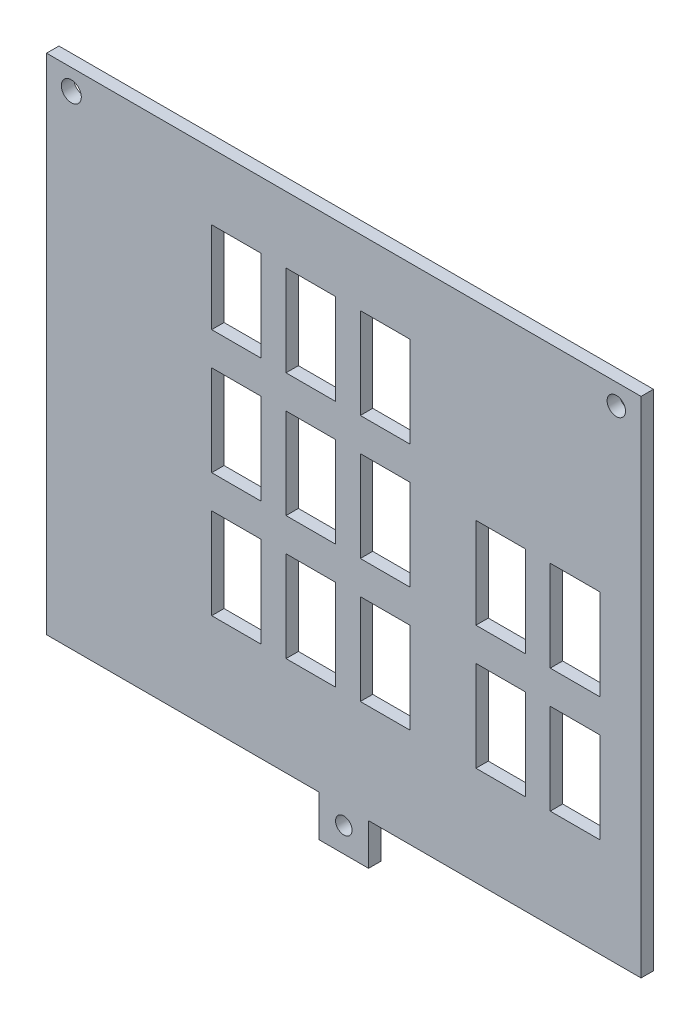
SolidWorks part; units mm, degrees
ref_plane "Plan de face" through (0, 0, 0) normal (0, 0, 1) x (1, 0, 0)
ref_plane "Plan de dessus" through (0, 0, 0) normal (0, 1, 0) x (1, 0, 0)
ref_plane "Plan de droite" through (0, 0, 0) normal (1, 0, 0) x (0, 0, -1)
sketch "Esquisse1" plane through (0, 0, 0) normal (0, 0, 1) x (1, 0, 0)
  line L0 (-67.585, 27.7309) -> (4.415, 27.7309)
  line L1 (4.415, 27.7309) -> (4.415, -33.2691)
  line L2 (4.415, -33.2691) -> (-67.585, -33.2691)
  line L3 (-67.585, -33.2691) -> (-67.585, 27.7309)
extrude "Boss.-Extru.1" add sketch "Esquisse1" along normal blind 1.5
sketch "Esquisse2" plane through (0, 0, 0) normal (0, 0, -1) x (-1, 0, 0)
  line L0 (-4.415, 27.7309) -> (67.585, 27.7309) construction
  line L1 (67.585, 27.7309) -> (67.585, -33.2691) construction
  line L2 (-4.415, -33.2691) -> (-4.415, 27.7309) construction
  circle A0 centre (-1.415, 25.2309) radius 1.1145
  circle A1 centre (64.585, 25.2309) radius 1.2071
  dimension "D1" = 2.5
  dimension "D2" = 2.5
  dimension "D3" = 3
  dimension "D4" = 3
extrude "Enlèv. mat.-Extru.1" cut sketch "Esquisse2" against normal through all
sketch "Esquisse4" plane through (0, 0, 0) normal (0, 0, -1) x (-1, 0, 0)
  line L0 (29.585, -21.2691) -> (29.585, -10.2691)
  line L1 (67.585, -33.2691) -> (-4.415, -33.2691) construction
  line L2 (29.585, -10.2691) -> (23.585, -10.2691)
  line L3 (29.585, 8.7309) -> (29.585, 19.7309)
  line L4 (67.585, 27.7309) -> (67.585, -33.2691) construction
  line L5 (23.585, -10.2691) -> (23.585, -21.2691)
  line L6 (47.585, -21.2691) -> (41.585, -21.2691)
  line L7 (41.585, -21.2691) -> (41.585, -10.2691)
  line L8 (41.585, -10.2691) -> (47.585, -10.2691)
  line L9 (47.585, -10.2691) -> (47.585, -21.2691)
  line L10 (23.585, -21.2691) -> (29.585, -21.2691)
  line L11 (38.585, -21.2691) -> (38.585, -10.2691)
  line L12 (38.585, -10.2691) -> (32.585, -10.2691)
  line L13 (32.585, -10.2691) -> (32.585, -21.2691)
  line L14 (32.585, -21.2691) -> (38.585, -21.2691)
  line L15 (47.585, -6.2691) -> (47.585, 4.7309)
  line L16 (47.585, 4.7309) -> (41.585, 4.7309)
  line L17 (41.585, 4.7309) -> (41.585, -6.2691)
  line L18 (41.585, -6.2691) -> (47.585, -6.2691)
  line L19 (38.585, -6.2691) -> (38.585, 4.7034)
  line L20 (38.585, 4.7034) -> (32.585, 4.7034)
  line L21 (32.585, 4.7034) -> (32.585, -6.2691)
  line L22 (32.585, -6.2691) -> (38.585, -6.2691)
  line L23 (29.585, -6.2691) -> (29.585, 4.7309)
  line L24 (29.585, 4.7309) -> (23.585, 4.7309)
  line L25 (23.585, 4.7309) -> (23.585, -6.2691)
  line L26 (23.585, -6.2691) -> (29.585, -6.2691)
  line L27 (29.585, 19.7309) -> (23.585, 19.7309)
  line L28 (23.585, 19.7309) -> (23.585, 8.7309)
  line L29 (23.585, 8.7309) -> (29.585, 8.7309)
  line L30 (38.585, 8.7034) -> (38.585, 19.7034)
  line L31 (38.585, 19.7034) -> (32.585, 19.7034)
  line L32 (32.585, 19.7034) -> (32.585, 8.7034)
  line L33 (32.585, 8.7034) -> (38.585, 8.7034)
  line L34 (47.585, 8.7309) -> (47.585, 19.7309)
  line L35 (47.585, 19.7309) -> (41.585, 19.7309)
  line L36 (41.585, 19.7309) -> (41.585, 8.7309)
  line L37 (41.585, 8.7309) -> (47.585, 8.7309)
  line L38 (15.585, -21.2691) -> (9.585, -21.2691)
  line L39 (9.585, -21.2691) -> (9.585, -10.2691)
  line L40 (9.585, -10.2691) -> (15.585, -10.2691)
  line L41 (15.585, -10.2691) -> (15.585, -21.2691)
  line L42 (6.585, -21.2691) -> (0.585, -21.2691)
  line L43 (0.585, -21.2691) -> (0.585, -10.2691)
  line L44 (0.585, -10.2691) -> (6.585, -10.2691)
  line L45 (6.585, -10.2691) -> (6.585, -21.2691)
  line L46 (15.585, -6.2691) -> (9.585, -6.2691)
  line L47 (9.585, -6.2691) -> (9.585, 4.7309)
  line L48 (9.585, 4.7309) -> (15.585, 4.7309)
  line L49 (15.585, 4.7309) -> (15.585, -6.2691)
  line L50 (6.585, -6.2691) -> (0.585, -6.2691)
  line L51 (0.585, -6.2691) -> (0.585, 4.7309)
  line L52 (0.585, 4.7309) -> (6.585, 4.7309)
  line L53 (6.585, 4.7309) -> (6.585, -6.2691)
  point P8 (35.585, -10.2691)
  point P28 (26.585, 4.7309)
  point P48 (26.585, 8.7309)
  point P65 (9.585, -15.7691)
  dimension "D1" = 20
  dimension "D2" = 6
  dimension "D3" = 6
  dimension "D4" = 3
  dimension "D5" = 11
  dimension "D6" = 3
  dimension "D7" = 12
  dimension "D8" = 4
  dimension "D9" = 3
  dimension "D10" = 3
  dimension "D11" = 4
  dimension "D12" = 4
  dimension "D13" = 12
  dimension "D14" = 12
  dimension "D15" = 4
  dimension "D16" = 4
  dimension "D17" = 4
  dimension "D18" = 3
  dimension "D19" = 3
  dimension "D20" = 20
  dimension "D21" = 20
  dimension "D22" = 6
  dimension "D23" = 6
  dimension "D24" = 6
  dimension "D25" = 6
  dimension "D26" = 6
  dimension "D27" = 6
  dimension "D28" = 6
  dimension "D29" = 11
  dimension "D30" = 11
  dimension "D31" = 11
  dimension "D32" = 11
  dimension "D33" = 11
  dimension "D34" = 12
  dimension "D35" = 12
  dimension "D36" = 11
  dimension "D37" = 6
  dimension "D38" = 11
  dimension "D39" = 8
  dimension "D40" = 3
  dimension "D41" = 6
  dimension "D42" = 11
  dimension "D43" = 11
  dimension "D44" = 6
  dimension "D45" = 6
  dimension "D46" = 11
  dimension "D47" = 8
  dimension "D48" = 3
  dimension "D49" = 4
  dimension "D50" = 4
extrude "Enlèv. mat.-Extru.2" cut sketch "Esquisse4" against normal through all contours L9 L8 L7 L6 | L13 L14 L11 L12 region at (-44.585, -15.7691, 0) region at (-35.585, -15.7691, 0)
extrude "Enlèv. mat.-Extru.3" cut sketch "Esquisse4<3>" against normal through all
sketch "Esquisse4<3>" plane through (0, 0, 0) normal (0, 0, -1) x (-1, 0, 0) same geometry as "Esquisse4"
sketch "Esquisse5" plane through (0, -33.2691, 0) normal (0, -1, 0) x (1, 0, 0)
  line L0 (-34.585, 1.5) -> (-34.585, 0)
  line L1 (-67.585, 1.5) -> (4.415, 1.5) construction
  line L2 (-67.585, 0) -> (4.415, 0) construction
  line L3 (-34.585, 0) -> (-28.585, 0)
  line L4 (-28.585, 1.5) -> (-28.585, 0)
  line L5 (4.415, 1.5) -> (4.415, 0) construction
  line L11 (-67.585, 0) -> (4.415, 0)
  line L12 (4.415, 0) -> (4.415, 1.5)
  line L13 (4.415, 1.5) -> (-67.585, 1.5)
  line L14 (-67.585, 1.5) -> (-67.585, 0)
  line L17 (-28.585, 1.5) -> (-34.585, 1.5)
  dimension "D1" = 6
  dimension "D2" = 33
  dimension "D3" = 0
extrude "Boss.-Extru.2" add sketch "Esquisse5" along normal blind 5
sketch "Esquisse6" plane through (0, 0, 1.5) normal (0, 0, 1) x (1, 0, 0)
  line L0 (-28.585, -38.2691) -> (-28.585, -33.2691) construction
  line L1 (-28.585, -38.2691) -> (-34.585, -38.2691) construction
  circle A0 centre (-31.585, -35.2691) radius 1
  dimension "D1" = 3
  dimension "D2" = 3
extrude "Enlèv. mat.-Extru.4" cut sketch "Esquisse6" against normal blind 6
